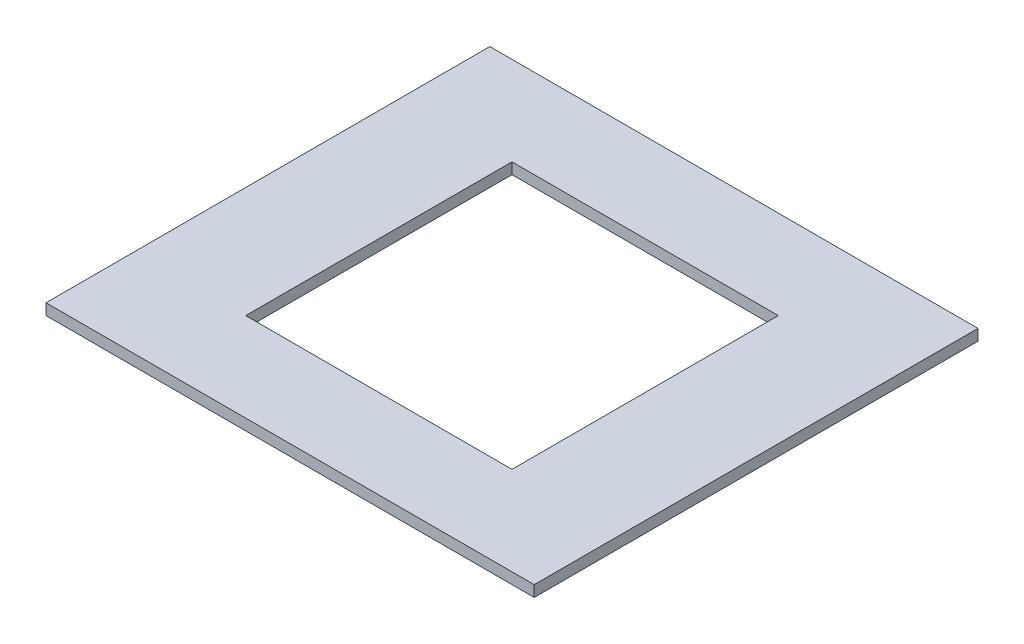
SolidWorks part; units mm, degrees
ref_plane "Front Plane" through (0, 0, 0) normal (0, 0, 1) x (1, 0, 0)
ref_plane "Top Plane" through (0, 0, 0) normal (0, 1, 0) x (1, 0, 0)
ref_plane "Right Plane" through (0, 0, 0) normal (1, 0, 0) x (0, 0, -1)
sketch "Sketch1" plane through (0, 0, 0) normal (0, 1, 0) x (1, 0, 0)
  line L1 (0, 0) -> (-139.7, 0)
  line L2 (0, 0) -> (0, 127)
  line L3 (0, 127) -> (-139.7, 127)
  line L4 (-139.7, 0) -> (-139.7, 127)
  line L5 (-107.95, 101.6) -> (-31.75, 101.6)
  line L6 (-107.95, 101.6) -> (-107.95, 25.4)
  line L7 (-107.95, 25.4) -> (-31.75, 25.4)
  line L8 (-31.75, 101.6) -> (-31.75, 25.4)
  dimension "D1" = 139.7
  dimension "D2" = 127
  dimension "D3" = 31.75
  dimension "D4" = 31.75
  dimension "D5" = 25.4
  dimension "D6" = 25.4
extrude "Boss-Extrude1" add sketch "Sketch1" along normal blind 3.175
